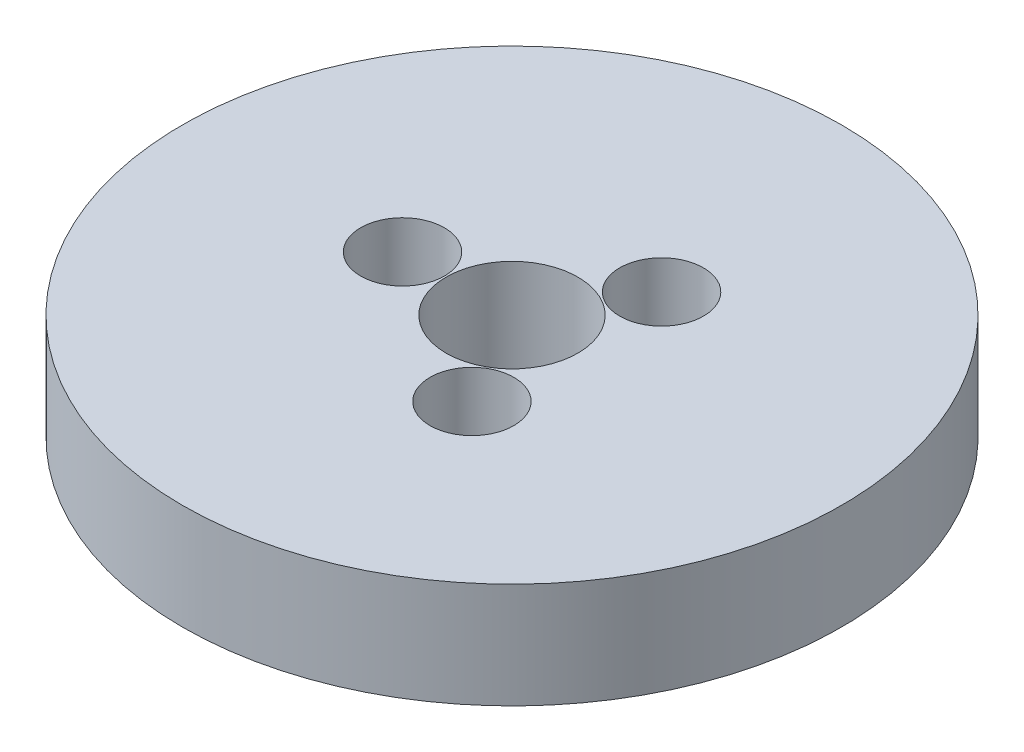
SolidWorks part; units mm, degrees
ref_plane "Front Plane" through (0, 0, 0) normal (0, 0, 1) x (1, 0, 0)
ref_plane "Top Plane" through (0, 0, 0) normal (0, 1, 0) x (1, 0, 0)
ref_plane "Right Plane" through (0, 0, 0) normal (1, 0, 0) x (0, 0, -1)
sketch "Sketch1" plane through (0, 0, 0) normal (0, 1, 0) x (1, 0, 0)
  circle A0 centre (0, 0) radius 50
  dimension "FLANGE_OD" = 100
extrude "Boss-Extrude1" add sketch "Sketch1" along normal blind 16
sketch "Sketch2" plane through (0, 0, 0) normal (0, 1, 0) x (1, 0, 0)
  circle A0 centre (0, 0) radius 10
  dimension "BORE_D" = 20
extrude "Cut-Extrude1" cut sketch "Sketch2" along normal through all
sketch "Sketch3" plane through (0, 16, 0) normal (0, 1, 0) x (1, 0, 0)
  circle A0 centre (0, 0) radius 16.6117 construction
  circle A1 centre (-16.6117, 0) radius 6.3554
  dimension "BOLT_D" = 12.7108
  dimension "BOLT_PCD" = 33.2233
extrude "Cut-Extrude2" cut sketch "Sketch3" against normal blind 11.2204
pattern_circular "CirPattern1" count 3 over 360 about axis through (0, 0, 0) along (0, 1, 0) of "Cut-Extrude2"
